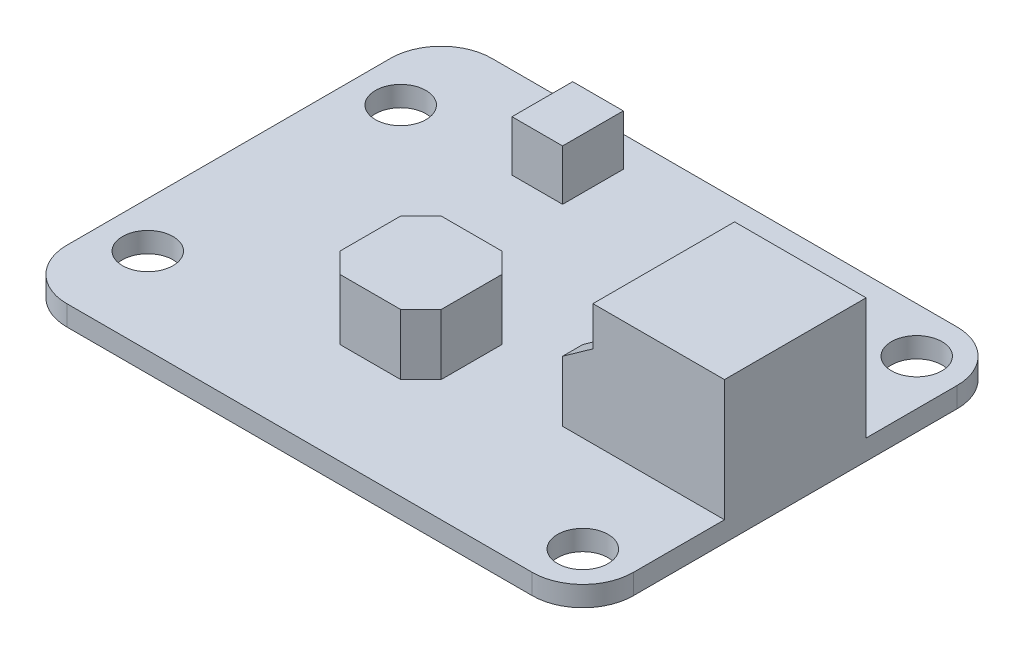
SolidWorks part; units mm, degrees
ref_plane "Alzado" through (0, 0, 0) normal (0, 0, 1) x (1, 0, 0)
ref_plane "Planta" through (0, 0, 0) normal (0, 1, 0) x (1, 0, 0)
ref_plane "Vista lateral" through (0, 0, 0) normal (1, 0, 0) x (0, 0, -1)
sketch "Croquis1" plane through (0, 0, 0) normal (0, 1, 0) x (1, 0, 0)
  line L1 (-11.5, -10.5) -> (11.5, -10.5)
  line L2 (-14, -8) -> (-14, 8)
  line L3 (-11.5, 10.5) -> (11.5, 10.5)
  line L4 (14, -8) -> (14, 8)
  line L5 (-14, -10.5) -> (14, 10.5) construction
  line L6 (-14, 10.5) -> (14, -10.5) construction
  arc A0 (11.5, 10.5) -> (14, 8) centre (11.5, 8) cw
  arc A1 (11.5, -10.5) -> (14, -8) centre (11.5, -8) ccw
  arc A2 (-11.5, -10.5) -> (-14, -8) centre (-11.5, -8) cw
  arc A3 (-14, 8) -> (-11.5, 10.5) centre (-11.5, 8) cw
  circle A4 centre (11.75, -8.25) radius 1.25
  circle A5 centre (11.75, 8.25) radius 1.25
  circle A6 centre (-11.75, 6.25) radius 1.25
  circle A7 centre (-11.75, -6.25) radius 1.25
  point P0 (0, 0)
  point P26 (0, 0)
  point P27 (0, 0)
  point P28 (12.9914, -15.5)
  point P29 (0, 0)
  point P30 (0, 0)
  dimension "D3" = 2.5
  dimension "D4" = 2.5
  dimension "D5" = 2.5
  dimension "D6" = 2.5
  dimension "D7" = 2.5
  dimension "D1" = 28
  dimension "D2" = 21
  dimension "D8" = 2.25
  dimension "D9" = 2.25
  dimension "D11" = 2.25
  dimension "D12" = 4.25
  dimension "D13" = 4.25
  dimension "D14" = 2.25
extrude "Saliente-Extruir1" add sketch "Croquis1" along normal blind 1
sketch "Croquis2" plane through (0, 1, 0) normal (0, 1, 0) x (1, 0, 0)
  line L0 (11.5, 10.5) -> (-11.5, 10.5) construction
  line L1 (14, -3.5) -> (6, -3.5)
  line L2 (14, -3.5) -> (14, 3.5)
  line L3 (14, 3.5) -> (6, 3.5)
  line L4 (6, -3.5) -> (6, -2.5)
  line L5 (14, -3.5) -> (6, 3.5) construction
  line L6 (14, 3.5) -> (6, -3.5) construction
  line L8 (14, -8) -> (14, 8) construction
  line L9 (6, 2.5) -> (7.5, 2.5)
  line L10 (7.5, 2.5) -> (7.5, -2.5)
  line L11 (7.5, -2.5) -> (6, -2.5)
  line L12 (6, 2.5) -> (6, 3.5)
  point P0 (10, 0)
  dimension "D1" = 8
  dimension "D2" = 7
  dimension "D3" = 7
  dimension "D4" = 1
  dimension "D5" = 1
  dimension "D6" = 1.5
extrude "Saliente-Extruir2" add sketch "Croquis2" along normal blind 6
sketch "Croquis3" plane through (0, 0, 3.5) normal (0, 0, 1) x (1, 0, 0)
  line L0 (7.5, 7) -> (7.5, 5.064)
  line L1 (7.5, 5.064) -> (6, 4)
  line L2 (6, 7) -> (6, 1) construction
  line L3 (6, 4) -> (6, 7)
  line L4 (6, 7) -> (7.5, 7)
  line L5 (-11.5, 1) -> (11.5, 1) construction
  dimension "D1" = 3
extrude "Cortar-Extruir1" cut sketch "Croquis3" against normal through all
sketch "Croquis4" plane through (0, 1, 0) normal (0, 1, 0) x (1, 0, 0)
  line L0 (-14, 8) -> (-14, -8) construction
  line L1 (-3, -5.5) -> (0, -5.5)
  line L2 (-4, -4.5) -> (-4, -1.5)
  line L3 (-3, -0.5) -> (0, -0.5)
  line L4 (1, -4.5) -> (1, -1.5)
  line L5 (-4, -5.5) -> (1, -0.5) construction
  line L6 (-4, -0.5) -> (1, -5.5) construction
  line L7 (-11.5, -10.5) -> (11.5, -10.5) construction
  line L8 (-4, -1.5) -> (-3, -0.5)
  line L9 (-4, -4.5) -> (-3, -5.5)
  line L10 (0, -5.5) -> (1, -4.5)
  line L11 (1, -1.5) -> (0, -0.5)
  point P0 (-1.5, -3)
  dimension "D1" = 10
  dimension "D2" = 5
  dimension "D3" = 5
  dimension "D4" = 1
  dimension "D5" = 1
  dimension "D6" = 1
  dimension "D7" = 1
  dimension "D8" = 1
  dimension "D9" = 1
  dimension "D10" = 1
  dimension "D11" = 1
  dimension "D12" = 5
extrude "Saliente-Extruir3" add sketch "Croquis4" along normal blind 3
sketch "Croquis5" plane through (0, 1, 0) normal (0, 1, 0) x (1, 0, 0)
  line L0 (11.5, 10.5) -> (-11.5, 10.5) construction
  line L1 (-6, 9) -> (-3.5, 9)
  line L2 (-6, 9) -> (-6, 6)
  line L3 (-6, 6) -> (-3.5, 6)
  line L4 (-3.5, 9) -> (-3.5, 6)
  line L5 (-6, 9) -> (-3.5, 6) construction
  line L6 (-6, 6) -> (-3.5, 9) construction
  line L7 (-14, 8) -> (-14, -8) construction
  point P0 (-4.75, 7.5)
  dimension "D1" = 1.5
  dimension "D2" = 8
  dimension "D3" = 2.5
  dimension "D4" = 3
extrude "Saliente-Extruir4" add sketch "Croquis5" along normal blind 2.5
